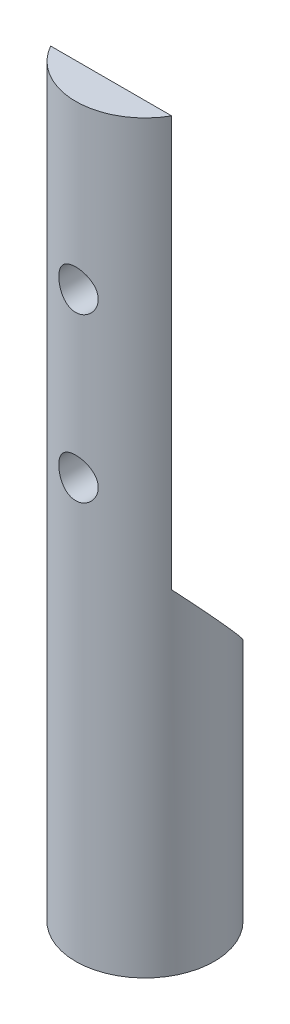
SolidWorks part; units mm, degrees
ref_plane "Front Plane" through (0, 0, 0) normal (0, 0, 1) x (1, 0, 0)
ref_plane "Top Plane" through (0, 0, 0) normal (0, 1, 0) x (1, 0, 0)
ref_plane "Right Plane" through (0, 0, 0) normal (1, 0, 0) x (0, 0, -1)
sketch "Sketch1" plane through (0, 0, 0) normal (0, 1, 0) x (1, 0, 0)
  circle A0 centre (0, 0) radius 3.9713
  dimension "D1" = 7.9426
extrude "Boss-Extrude1" add sketch "Sketch1" along normal blind 42.672
sketch "Sketch2" plane through (0, 0, 0) normal (1, 0, 0) x (0, 0, -1)
  line L0 (-3.9713, 40.162) -> (-3.9713, 46.9504) construction
  line L1 (-3.9713, 42.672) -> (-3.9713, 0) construction
  line L2 (-1.9393, 47.4841) -> (-1.9393, 19.1606)
  line L3 (-1.9393, 19.1606) -> (3.9713, 12.7)
  line L4 (3.9713, 12.7) -> (3.9713, 47.4841)
  line L5 (3.9713, 47.4841) -> (-1.9393, 47.4841)
  line L6 (-3.9713, 0) -> (3.9713, 0) construction
  line L7 (3.9713, 0) -> (3.9713, 42.672) construction
  dimension "D1" = 4.064
  dimension "D2" = 12.7
extrude "Cut-Extrude1" cut sketch "Sketch2" against normal through all and the other way through all
sketch "Sketch3" plane through (0, 0, 1.9393) normal (0, 0, -1) x (-1, 0, 0)
  line L0 (0, 42.672) -> (0, 25.8171) construction
  line L1 (3.4656, 42.672) -> (-3.4656, 42.672) construction
  point P5 (0, 33.332)
  point P6 (0, 23.992)
  dimension "D1" = 9.34
  dimension "D2" = 9.34
hole_wizard "#4-40 Tapped Hole1" positions "Sketch5" profile "Sketch4" tap size "#4-40" standard "Ansi Inch" end condition through all
sketch "Sketch5" plane through (0, 0, 1.9393) normal (0, 0, -1) x (-1, 0, 0)
  point P1 (0, 23.992)
  point P4 (0, 33.332)
sketch "Sketch4" plane through (0, 23.992, 1.9393) normal (1, 0, 0) x (0, 1, 0)
  line L0 (0, 0) -> (0, 2.032)
  line L1 (0, 2.032) -> (1.1303, 2.032)
  line L2 (1.1303, 2.032) -> (1.1303, 0)
  line L5 (1.1303, 0) -> (0, 0)
  line L11 (0, -6.35) -> (0, 107.95) construction
  dimension "Thru Tap Drill Dia." = 2.2606
  dimension "Thru Tap Drill Depth" = 2.032
cosmetic thread "Hole Thread1" parameters "D2"=2.8448
cosmetic thread "Hole Thread2" parameters "D2"=2.8448
